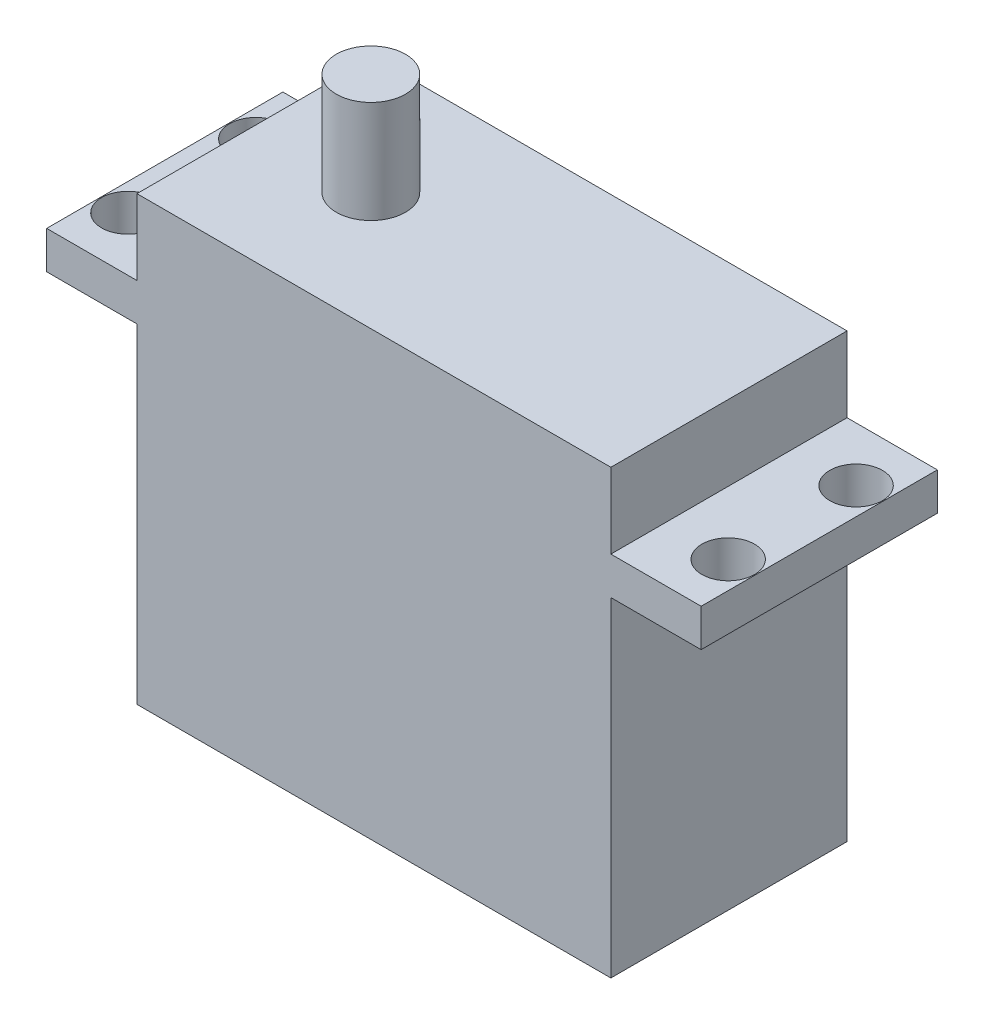
SolidWorks part; units mm, degrees
ref_plane "Front Plane" through (0, 0, 0) normal (0, 0, 1) x (1, 0, 0)
ref_plane "Top Plane" through (0, 0, 0) normal (0, 1, 0) x (1, 0, 0)
ref_plane "Right Plane" through (0, 0, 0) normal (1, 0, 0) x (0, 0, -1)
sketch "Sketch1" plane through (0, 0, 0) normal (0, 1, 0) x (1, 0, 0)
  line L1 (0, 0) -> (40.005, 0)
  line L2 (0, 0) -> (0, 19.939)
  line L3 (0, 19.939) -> (40.005, 19.939)
  line L4 (40.005, 0) -> (40.005, 19.939)
  dimension "D1" = 40.005
  dimension "D2" = 19.939
extrude "Boss-Extrude1" add sketch "Sketch1" along normal blind 37.338
sketch "Sketch2" plane through (40.005, 0, 0) normal (1, 0, 0) x (0, 0, -1)
  line L0 (0, 37.338) -> (0, 0) construction
  line L1 (0, 30.988) -> (19.939, 30.988)
  line L2 (0, 30.988) -> (0, 27.813)
  line L3 (0, 27.813) -> (19.939, 27.813)
  line L4 (19.939, 30.988) -> (19.939, 27.813)
  line L5 (19.939, 37.338) -> (19.939, 0) construction
  line L6 (0, 37.338) -> (19.939, 37.338) construction
  dimension "D1" = 6.35
  dimension "D2" = 3.175
extrude "Boss-Extrude2" add sketch "Sketch2" along normal blind 7.62
sketch "Sketch3" plane through (0, 30.988, 0) normal (0, 1, 0) x (1, 0, 0)
  line L0 (45.339, 15.367) -> (45.339, 4.572) construction
  line L1 (47.625, 19.939) -> (47.625, 0) construction
  line L2 (47.625, 19.939) -> (40.005, 19.939) construction
  circle A0 centre (45.339, 15.367) radius 2.2225
  circle A1 centre (45.339, 4.572) radius 2.2225
  point P4 (45.339, 9.9695)
  point P5 (47.625, 9.9695)
  point P6 (45.339, 6.7945)
  point P9 (45.339, 13.1445)
  point P10 (43.815, 19.939)
  dimension "D2" = 4.445
  dimension "D1" = 6.35
  dimension "D3" = 2.286
extrude "Cut-Extrude1" cut sketch "Sketch3" against normal through all
ref_plane "Plane1" through (20.0025, 0, 0) normal (1, 0, 0) x (0, 0, -1)
mirror "Mirror1" about plane through (20.0025, 0, 0) normal (1, 0, 0) of "Cut-Extrude1", "Boss-Extrude2"
sketch "Sketch4" plane through (0, 37.338, 0) normal (0, 1, 0) x (1, 0, 0)
  line L0 (-7.62, 19.939) -> (-7.62, 0) construction
  circle A0 centre (9.779, 9.9695) radius 2.921
  point P2 (-7.62, 9.9695)
  point P3 (12.7, 9.9695)
  dimension "D2" = 5.842
  dimension "D1" = 20.32
extrude "Boss-Extrude3" add sketch "Sketch4" along normal blind 8.636
